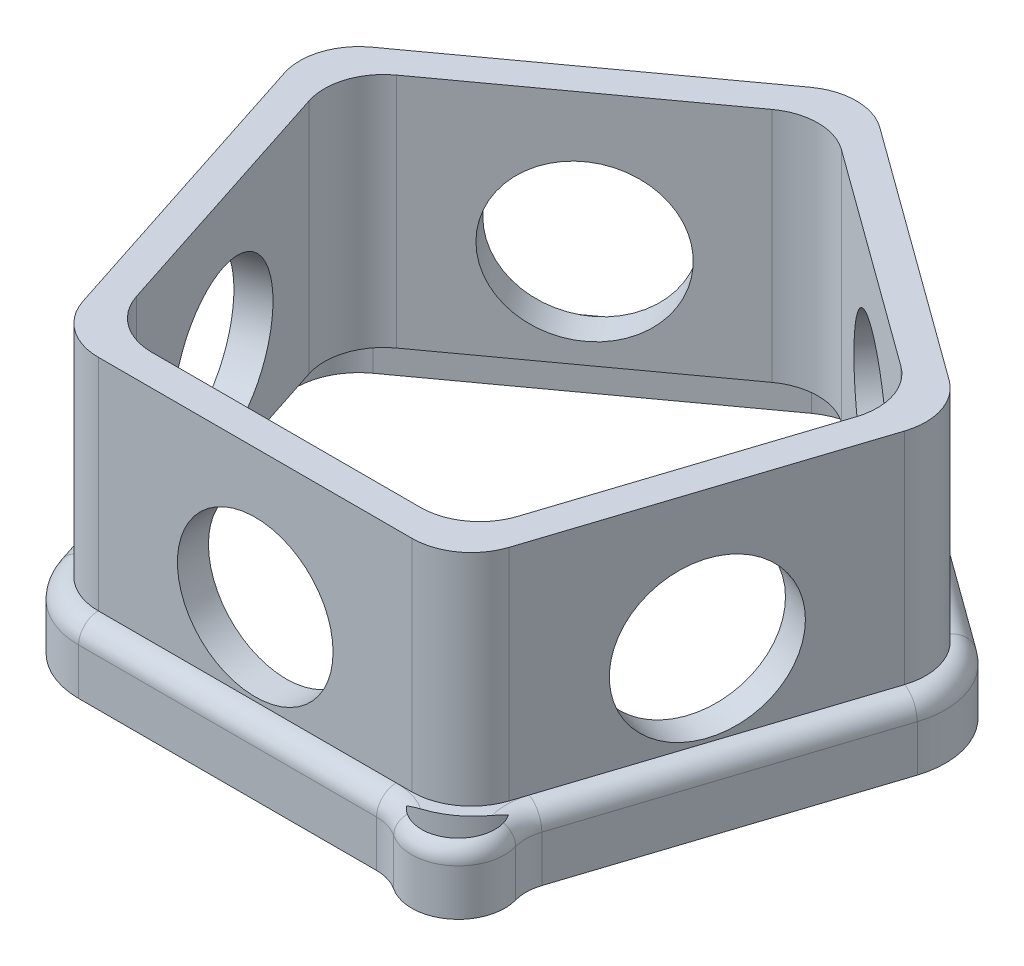
SolidWorks part; units mm, degrees
material "ABS"
ref_plane "Front Plane" through (0, 0, 0) normal (0, 0, 1) x (1, 0, 0)
ref_plane "Top Plane" through (0, 0, 0) normal (0, 1, 0) x (1, 0, 0)
ref_plane "Right Plane" through (0, 0, 0) normal (1, 0, 0) x (0, 0, -1)
sketch "Sketch1" plane through (0, 0, 0) normal (0, 0, 1) x (1, 0, 0)
  line L1 (-22.86, -12.7) -> (22.86, -12.7)
  line L2 (-22.86, -12.7) -> (-22.86, 12.7)
  line L3 (-22.86, 12.7) -> (22.86, 12.7)
  line L4 (22.86, -12.7) -> (22.86, 12.7)
  line L5 (-22.86, -12.7) -> (22.86, 12.7) construction
  line L6 (-22.86, 12.7) -> (22.86, -12.7) construction
  circle A0 centre (0, 0) radius 9.75
  dimension "D1" = 19.5
  dimension "D2" = 45.72
  dimension "D3" = 25.4
extrude "Boss-Extrude1" add sketch "Sketch1" along normal blind 4
sketch "Sketch2" plane through (0, 12.7, 0) normal (0, 1, 0) x (1, 0, 0)
  line L0 (22.86, 0) -> (36.9883, 43.4823)
  line L1 (36.9883, 43.4823) -> (0, 70.3558)
  line L2 (0, 70.3558) -> (-36.9883, 43.4823)
  line L3 (-36.9883, 43.4823) -> (-22.86, 0)
  line L4 (-22.86, 0) -> (22.86, 0)
  line L6 (-41.6905, 45.0102) -> (-25.7662, -4)
  line L7 (-25.7662, -4) -> (25.7662, -4)
  line L8 (25.7662, -4) -> (41.6905, 45.0102)
  line L9 (41.6905, 45.0102) -> (0, 75.3001)
  line L10 (0, 75.3001) -> (-41.6905, 45.0102)
  line L11 (-22.86, 0) -> (-22.86, -4)
  line L12 (-22.86, -4) -> (22.86, 0)
  line L13 (22.86, -4) -> (22.86, 0)
  line M7 (-22.86, 0) -> (-22.86, -4)
  line M9 (22.86, -4) -> (22.86, 0)
  dimension "D1" = 108
  dimension "D2" = 108
  dimension "D3" = 4
extrude "Boss-Extrude2" add sketch "Sketch2" against normal up to surface (25.4 mm away) contours L9 L10 L6 L7 L3 L2 L1 L0 L8 M7 M9 region at (31.0185, 12.7, -21.3856) up to face at (0, -12.7, 2)
sketch "Sketch3" plane through (0, 0, 4) normal (0, 0, 1) x (1, 0, 0)
  circle A0 centre (0, 0) radius 10.033
  dimension "D1" = 20.066
extrude "Cut-Extrude1" cut sketch "Sketch3" against normal blind 11.62
sketch "Sketch4" plane through (0, 12.7, 0) normal (0, 1, 0) x (1, 0, 0)
  line L0 (0, 70.3558) -> (0, 0)
  line L1 (22.86, 0) -> (-22.86, 0) construction
  line L2 (36.9883, 43.4823) -> (-29.9241, 21.7412)
  line L3 (-36.9883, 43.4823) -> (-22.86, 0) construction
sketch "Sketch5" plane through (0, 0, 0) normal (1, 0, 0) x (0, 0, -1)
  line L0 (43.4823, 12.7) -> (21.7412, 12.7) construction
  line L1 (43.4823, 12.7) -> (21.7412, 12.7)
  line L2 (31.5133, 12.7) -> (31.5133, 7.2346)
pattern_circular "CirPattern1" count 5 over 360 about axis through (0, 12.7, -31.5133) along (0, -1, 0) of "Cut-Extrude1"
fillet "Fillet1" radius 7.62 10 edges at (-22.86, 0, 0) (-36.9883, 0, -43.4823) (0, 0, -70.3558) (36.9883, 0, -43.4823) (22.86, 0, 0) (25.7662, 0, 4) (41.6905, 0, -45.0102) (0, 0, -75.3001) (-41.6905, 0, -45.0102) (-25.7662, 0, 4)
sketch "Sketch6" plane through (0, 12.7, 0) normal (0, 1, 0) x (1, 0, 0)
  line L0 (24.5708, 5.2653) -> (35.2775, 38.217) construction
  line L1 (17.3237, 0) -> (-17.3237, 0) construction
  line L2 (-35.2775, 38.217) -> (-24.5708, 5.2653) construction
  line L3 (-4.4789, 67.1017) -> (-32.5093, 46.7364) construction
  line L4 (32.5093, 46.7364) -> (4.4789, 67.1017) construction
  line L5 (-20.2299, -4) -> (20.2299, -4)
  line L6 (27.477, 1.2653) -> (39.9797, 39.7449)
  line L7 (37.2116, 48.2643) -> (4.4789, 72.046)
  line L8 (-4.4789, 72.046) -> (-37.2116, 48.2643)
  line L9 (-39.9797, 39.7449) -> (-27.477, 1.2653)
  line L10 (-20.2299, -4) -> (20.2299, -4)
  line L11 (27.477, 1.2653) -> (39.9797, 39.7449)
  line L12 (37.2116, 48.2643) -> (4.4789, 72.046)
  line L13 (-4.4789, 72.046) -> (-37.2116, 48.2643)
  line L14 (-39.9797, 39.7449) -> (-27.477, 1.2653)
  line L15 (24.5708, 5.2653) -> (35.2775, 38.217)
  line L16 (17.3237, 0) -> (-17.3237, 0)
  line L17 (-35.2775, 38.217) -> (-24.5708, 5.2653)
  line L18 (-4.4789, 67.1017) -> (-32.5093, 46.7364)
  line L19 (32.5093, 46.7364) -> (4.4789, 67.1017)
  arc A0 (35.2775, 38.217) -> (32.5093, 46.7364) centre (28.0304, 40.5717) ccw construction
  arc A1 (17.3237, 0) -> (24.5708, 5.2653) centre (17.3237, 7.62) ccw construction
  arc A2 (-24.5708, 5.2653) -> (-17.3237, 0) centre (-17.3237, 7.62) ccw construction
  arc A3 (-32.5093, 46.7364) -> (-35.2775, 38.217) centre (-28.0304, 40.5717) ccw construction
  arc A4 (4.4789, 67.1017) -> (-4.4789, 67.1017) centre (0, 60.937) ccw construction
  arc A5 (20.2299, -4) -> (27.477, 1.2653) centre (20.2299, 3.62) ccw
  arc A6 (39.9797, 39.7449) -> (37.2116, 48.2643) centre (32.7327, 42.0996) ccw
  arc A7 (4.4789, 72.046) -> (-4.4789, 72.046) centre (0, 65.8813) ccw
  arc A8 (-37.2116, 48.2643) -> (-39.9797, 39.7449) centre (-32.7327, 42.0996) ccw
  arc A9 (-27.477, 1.2653) -> (-20.2299, -4) centre (-20.2299, 3.62) ccw
  arc A10 (20.2299, -4) -> (27.477, 1.2653) centre (20.2299, 3.62) ccw
  arc A11 (39.9797, 39.7449) -> (37.2116, 48.2643) centre (32.7327, 42.0996) ccw
  arc A12 (4.4789, 72.046) -> (-4.4789, 72.046) centre (0, 65.8813) ccw
  arc A13 (-37.2116, 48.2643) -> (-39.9797, 39.7449) centre (-32.7327, 42.0996) ccw
  arc A14 (-27.477, 1.2653) -> (-20.2299, -4) centre (-20.2299, 3.62) ccw
  arc A15 (35.2775, 38.217) -> (32.5093, 46.7364) centre (28.0304, 40.5717) ccw
  arc A16 (17.3237, 0) -> (24.5708, 5.2653) centre (17.3237, 7.62) ccw
  arc A17 (-24.5708, 5.2653) -> (-17.3237, 0) centre (-17.3237, 7.62) ccw
  arc A18 (-32.5093, 46.7364) -> (-35.2775, 38.217) centre (-28.0304, 40.5717) ccw
  arc A19 (4.4789, 67.1017) -> (-4.4789, 67.1017) centre (0, 60.937) ccw
  dimension "D5" = 7.62
  dimension "D6" = 7.62
  dimension "D2" = 4
  dimension "D3" = 40.4598
  dimension "D4" = 34.6475
  dimension "D1" = 0
extrude "Boss-Extrude3" add sketch "Sketch6" along normal blind 5.08
sketch "Sketch7" plane through (-35.8073, 0, -49.2846) normal (-0.5878, 0, -0.809) x (-0.809, 0, 0.5878)
  line L0 (-18.4941, 17.78) -> (-18.4941, 13.97)
  line L1 (-38.724, 17.78) -> (1.7358, 17.78) construction
  circle A0 centre (-18.4941, 13.97) radius 2.5
  dimension "D1" = 5
  dimension "D2" = 3.81
sketch "Sketch8" plane through (0, -12.7, 0) normal (0, -1, 0) x (1, 0, 0)
  line L0 (-27.477, -1.2653) -> (-39.9797, -39.7449) construction
  line L1 (-27.477, -1.2653) -> (-39.9797, -39.7449)
  line L7 (39.9797, -39.7449) -> (27.477, -1.2653)
  line L8 (20.2299, 4) -> (-20.2299, 4)
  line L9 (-27.477, -1.2653) -> (-39.9797, -39.7449)
  line L10 (-37.2116, -48.2643) -> (-4.4789, -72.046)
  line L11 (4.4789, -72.046) -> (37.2116, -48.2643)
  line L12 (39.9797, -39.7449) -> (27.477, -1.2653)
  line L13 (20.2299, 4) -> (-20.2299, 4)
  line L14 (-27.477, -1.2653) -> (-39.9797, -39.7449)
  line L15 (-37.2116, -48.2643) -> (-4.4789, -72.046)
  line L16 (4.4789, -72.046) -> (37.2116, -48.2643)
  line L22 (42.3954, -38.96) -> (29.8927, -0.4804)
  line L23 (20.2299, 6.54) -> (-20.2299, 6.54)
  line L24 (-29.8927, -0.4804) -> (-42.3954, -38.96)
  line L25 (-38.7046, -50.3192) -> (-5.9719, -74.1009)
  line L26 (5.9719, -74.1009) -> (38.7046, -50.3192)
  line L27 (42.3954, -38.96) -> (29.8927, -0.4804)
  line L28 (20.2299, 6.54) -> (-20.2299, 6.54)
  line L29 (-29.8927, -0.4804) -> (-42.3954, -38.96)
  line L30 (-38.7046, -50.3192) -> (-5.9719, -74.1009)
  line L31 (5.9719, -74.1009) -> (38.7046, -50.3192)
  arc A5 (27.477, -1.2653) -> (20.2299, 4) centre (20.2299, -3.62) ccw
  arc A6 (-20.2299, 4) -> (-27.477, -1.2653) centre (-20.2299, -3.62) ccw
  arc A7 (-39.9797, -39.7449) -> (-37.2116, -48.2643) centre (-32.7327, -42.0996) ccw
  arc A8 (-4.4789, -72.046) -> (4.4789, -72.046) centre (0, -65.8813) ccw
  arc A9 (37.2116, -48.2643) -> (39.9797, -39.7449) centre (32.7327, -42.0996) ccw
  arc A10 (27.477, -1.2653) -> (20.2299, 4) centre (20.2299, -3.62) ccw
  arc A11 (-20.2299, 4) -> (-27.477, -1.2653) centre (-20.2299, -3.62) ccw
  arc A12 (-39.9797, -39.7449) -> (-37.2116, -48.2643) centre (-32.7327, -42.0996) ccw
  arc A13 (-4.4789, -72.046) -> (4.4789, -72.046) centre (0, -65.8813) ccw
  arc A14 (37.2116, -48.2643) -> (39.9797, -39.7449) centre (32.7327, -42.0996) ccw
  arc A20 (29.8927, -0.4804) -> (20.2299, 6.54) centre (20.2299, -3.62) ccw
  arc A21 (-20.2299, 6.54) -> (-29.8927, -0.4804) centre (-20.2299, -3.62) ccw
  arc A22 (-42.3954, -38.96) -> (-38.7046, -50.3192) centre (-32.7327, -42.0996) ccw
  arc A23 (-5.9719, -74.1009) -> (5.9719, -74.1009) centre (0, -65.8813) ccw
  arc A24 (38.7046, -50.3192) -> (42.3954, -38.96) centre (32.7327, -42.0996) ccw
  arc A25 (29.8927, -0.4804) -> (20.2299, 6.54) centre (20.2299, -3.62) ccw
  arc A26 (-20.2299, 6.54) -> (-29.8927, -0.4804) centre (-20.2299, -3.62) ccw
  arc A27 (-42.3954, -38.96) -> (-38.7046, -50.3192) centre (-32.7327, -42.0996) ccw
  arc A28 (-5.9719, -74.1009) -> (5.9719, -74.1009) centre (0, -65.8813) ccw
  arc A29 (38.7046, -50.3192) -> (42.3954, -38.96) centre (32.7327, -42.0996) ccw
  line M31 (39.9797, -39.7449) -> (27.477, -1.2653)
  arc M32 (27.477, -1.2653) -> (20.2299, 4) centre (20.2299, -3.62) ccw
  line M33 (20.2299, 4) -> (-20.2299, 4)
  arc M34 (-20.2299, 4) -> (-27.477, -1.2653) centre (-20.2299, -3.62) ccw
  line M35 (-27.477, -1.2653) -> (-39.9797, -39.7449)
  arc M36 (-39.9797, -39.7449) -> (-37.2116, -48.2643) centre (-32.7327, -42.0996) ccw
  line M37 (-37.2116, -48.2643) -> (-4.4789, -72.046)
  arc M38 (-4.4789, -72.046) -> (4.4789, -72.046) centre (0, -65.8813) ccw
  line M39 (4.4789, -72.046) -> (37.2116, -48.2643)
  arc M40 (37.2116, -48.2643) -> (39.9797, -39.7449) centre (32.7327, -42.0996) ccw
  dimension "D1" = 0
  dimension "D2" = 2.54
extrude "Boss-Extrude4" add sketch "Sketch8" along normal blind 6.35 and the other way blind 2.159 contours L31 A29 L27 A25 L28 A26 L29 A27 L30 A28 M31 M40 M39 M38 M37 M36 M35 M34 M33 M32 region at (41.263, -12.7, -44.8712)
sketch "Sketch9" plane through (-37.3003, 0, -51.3395) normal (-0.5878, 0, -0.809) x (-0.809, 0, 0.5878)
  line L0 (1.7358, -12.7) -> (-38.724, -12.7) construction
  line L1 (1.7358, -12.7) -> (-38.724, -12.7)
  line L2 (-18.4941, -12.7) -> (-18.4941, -16.51)
  circle A0 centre (-18.4941, -16.51) radius 1.7
  dimension "D2" = 3.4
  dimension "D1" = 3.81
sketch "Sketch11" plane through (0, -19.05, 0) normal (0, -1, 0) x (1, 0, 0)
  line L0 (20.2299, 6.54) -> (19.9488, 5.4149)
  line L1 (19.9488, 5.4149) -> (27.19, 1.5678)
  line L2 (27.19, 1.5678) -> (29.8927, -0.4804)
  line L5 (5.9719, -74.1009) -> (38.7046, -50.3192)
  line L6 (42.3954, -38.96) -> (29.8927, -0.4804)
  line L7 (20.2299, 6.54) -> (-20.2299, 6.54)
  line L8 (-29.8927, -0.4804) -> (-42.3954, -38.96)
  line L9 (-38.7046, -50.3192) -> (-5.9719, -74.1009)
  line L10 (5.9719, -74.1009) -> (38.7046, -50.3192)
  line L11 (42.3954, -38.96) -> (29.8927, -0.4804)
  line L12 (20.2299, 6.54) -> (-20.2299, 6.54)
  line L13 (-29.8927, -0.4804) -> (-42.3954, -38.96)
  line L14 (-38.7046, -50.3192) -> (-5.9719, -74.1009)
  arc A0 (20.2299, 6.54) -> (29.8927, -0.4804) centre (24.6642, 2.4832) cw
  arc A5 (38.7046, -50.3192) -> (42.3954, -38.96) centre (32.7327, -42.0996) ccw
  arc A6 (29.8927, -0.4804) -> (20.2299, 6.54) centre (20.2299, -3.62) ccw
  arc A7 (-20.2299, 6.54) -> (-29.8927, -0.4804) centre (-20.2299, -3.62) ccw
  arc A8 (-42.3954, -38.96) -> (-38.7046, -50.3192) centre (-32.7327, -42.0996) ccw
  arc A9 (-5.9719, -74.1009) -> (5.9719, -74.1009) centre (0, -65.8813) ccw
  arc A10 (38.7046, -50.3192) -> (42.3954, -38.96) centre (32.7327, -42.0996) ccw
  arc A12 (-20.2299, 6.54) -> (-29.8927, -0.4804) centre (-20.2299, -3.62) ccw
  arc A13 (-42.3954, -38.96) -> (-38.7046, -50.3192) centre (-32.7327, -42.0996) ccw
  arc A14 (-5.9719, -74.1009) -> (5.9719, -74.1009) centre (0, -65.8813) ccw
  arc M24 (29.8927, -0.4804) -> (20.2299, 6.54) centre (20.2299, -3.62) ccw
  dimension "D1" = 0
extrude "Boss-Extrude5" add sketch "Sketch11" against normal up to surface (8.509 mm away) contours L1 L2 L0 M24 | A0 M24 region at (24.8084, -19.05, 3.8811) region at (26.7924, -19.05, 5.4124) up to face at (0, -10.541, -31.4641)
sketch "Sketch12" plane through (0, -19.05, 0) normal (0, -1, 0) x (1, 0, 0)
  line L0 (20.2299, 6.54) -> (20.2299, 4)
  line L1 (29.8927, -0.4804) -> (27.477, -1.2653)
  line L10 (5.9719, -74.1009) -> (38.7046, -50.3192)
  line L11 (42.3954, -38.96) -> (29.8927, -0.4804)
  line L12 (20.2299, 6.54) -> (-20.2299, 6.54)
  line L13 (-29.8927, -0.4804) -> (-42.3954, -38.96)
  line L14 (-38.7046, -50.3192) -> (-5.9719, -74.1009)
  line L15 (42.3954, -38.96) -> (29.8927, -0.4804)
  line L16 (42.3954, -38.96) -> (29.8927, -0.4804)
  line L17 (20.2299, 6.54) -> (-20.2299, 6.54)
  line L18 (20.2299, 6.54) -> (-20.2299, 6.54)
  line L19 (-29.8927, -0.4804) -> (-42.3954, -38.96)
  line L20 (-29.8927, -0.4804) -> (-42.3954, -38.96)
  line L23 (-38.7046, -50.3192) -> (-5.9719, -74.1009)
  line L24 (-38.7046, -50.3192) -> (-5.9719, -74.1009)
  line L25 (5.9719, -74.1009) -> (38.7046, -50.3192)
  line L26 (5.9719, -74.1009) -> (38.7046, -50.3192)
  arc A0 (27.477, -1.2653) -> (20.2299, 4) centre (20.2299, -3.62) ccw construction
  arc A1 (27.477, -1.2653) -> (20.2299, 4) centre (20.2299, -3.62) ccw
  arc A2 (29.8927, -0.4804) -> (20.2299, 6.54) centre (24.6642, 2.4832) ccw
  arc A4 (29.8927, -0.4804) -> (20.2299, 6.54) centre (24.6642, 2.4832) ccw
  arc A6 (28.7878, 0.1459) -> (21.1669, 5.6827) centre (24.6642, 2.4832) ccw
  arc A7 (21.1669, 5.6827) -> (28.7878, 0.1459) centre (19.5024, -4.6213) cw
  arc A14 (38.7046, -50.3192) -> (42.3954, -38.96) centre (32.7327, -42.0996) ccw
  arc A15 (29.8927, -0.4804) -> (20.2299, 6.54) centre (20.2299, -3.62) ccw
  arc A16 (-20.2299, 6.54) -> (-29.8927, -0.4804) centre (-20.2299, -3.62) ccw
  arc A17 (-42.3954, -38.96) -> (-38.7046, -50.3192) centre (-32.7327, -42.0996) ccw
  arc A18 (-5.9719, -74.1009) -> (5.9719, -74.1009) centre (0, -65.8813) ccw
  arc A22 (-20.2299, 6.54) -> (-29.8927, -0.4804) centre (-20.2299, -3.62) ccw
  arc A23 (-20.2299, 6.54) -> (-29.8927, -0.4804) centre (-20.2299, -3.62) ccw
  arc A24 (-42.3954, -38.96) -> (-38.7046, -50.3192) centre (-32.7327, -42.0996) ccw
  arc A25 (-42.3954, -38.96) -> (-38.7046, -50.3192) centre (-32.7327, -42.0996) ccw
  arc A26 (-5.9719, -74.1009) -> (5.9719, -74.1009) centre (0, -65.8813) ccw
  arc A27 (-5.9719, -74.1009) -> (5.9719, -74.1009) centre (0, -65.8813) ccw
  arc A28 (38.7046, -50.3192) -> (42.3954, -38.96) centre (32.7327, -42.0996) ccw
  arc A29 (38.7046, -50.3192) -> (42.3954, -38.96) centre (32.7327, -42.0996) ccw
  dimension "D1" = 0
  dimension "D3" = 1.27
extrude "Cut-Extrude4" cut sketch "Sketch12" against normal blind 12.192 contours A6 | A6 A7 region at (25.7101, -19.05, 3.9228) region at (26.5903, -19.05, 5.1343)
fillet "Fillet5" radius 5.715 2 edges at (29.8927, -14.7955, -0.4804) (20.2299, -14.7955, 6.54)
fillet "Fillet6" radius 2.54 12 edges at (42.3954, -10.541, -45.2392) (22.3382, -10.541, -62.21) (0, -10.541, -76.0413) (-22.3382, -10.541, -62.21) (-42.3954, -10.541, -45.2392) (-36.144, -10.541, -19.7202) (-26.2018, -10.541, 4.5996) (-1.0228, -10.541, 6.54) (19.8337, -10.541, 6.7832) (30.2464, -10.541, -0.782) (36.4601, -10.541, -20.6929) (28.1967, -10.541, 7.3454)
sketch "Sketch13" plane through (0, -19.05, 0) normal (0, -1, 0) x (1, 0, 0)
  line L0 (20.2299, 4.6) -> (-20.2299, 4.6)
  line L1 (-28.0476, -1.0799) -> (-40.5504, -39.5595)
  line L2 (-37.5643, -48.7497) -> (-4.8316, -72.5314)
  line L3 (4.8316, -72.5314) -> (37.5643, -48.7497)
  line L4 (40.5504, -39.5595) -> (28.0476, -1.0799)
  line L5 (39.9797, -39.7449) -> (27.477, -1.2653)
  line L6 (4.4789, -72.046) -> (37.2116, -48.2643)
  line L7 (-37.2116, -48.2643) -> (-4.4789, -72.046)
  line L8 (-27.477, -1.2653) -> (-39.9797, -39.7449)
  line L9 (20.2299, 4) -> (-20.2299, 4)
  line L10 (39.9797, -39.7449) -> (27.477, -1.2653)
  line L11 (4.4789, -72.046) -> (37.2116, -48.2643)
  line L12 (-37.2116, -48.2643) -> (-4.4789, -72.046)
  line L13 (-27.477, -1.2653) -> (-39.9797, -39.7449)
  line L14 (20.2299, 4) -> (-20.2299, 4)
  arc A0 (-20.2299, 4.6) -> (-28.0476, -1.0799) centre (-20.2299, -3.62) ccw
  arc A1 (-40.5504, -39.5595) -> (-37.5643, -48.7497) centre (-32.7327, -42.0996) ccw
  arc A2 (28.7878, 0.1459) -> (21.1669, 5.6827) centre (24.6642, 2.4832) ccw
  arc A3 (28.7878, 0.1459) -> (21.1669, 5.6827) centre (19.5024, -4.6213) ccw
  arc A4 (28.7878, 0.1459) -> (21.1669, 5.6827) centre (24.6642, 2.4832) ccw
  arc A5 (37.2116, -48.2643) -> (39.9797, -39.7449) centre (32.7327, -42.0996) ccw
  arc A6 (-4.4789, -72.046) -> (4.4789, -72.046) centre (0, -65.8813) ccw
  arc A7 (-39.9797, -39.7449) -> (-37.2116, -48.2643) centre (-32.7327, -42.0996) ccw
  arc A8 (-20.2299, 4) -> (-27.477, -1.2653) centre (-20.2299, -3.62) ccw
  arc A9 (27.477, -1.2653) -> (20.2299, 4) centre (20.2299, -3.62) ccw
  arc A10 (37.2116, -48.2643) -> (39.9797, -39.7449) centre (32.7327, -42.0996) ccw
  arc A11 (-4.4789, -72.046) -> (4.4789, -72.046) centre (0, -65.8813) ccw
  arc A12 (-39.9797, -39.7449) -> (-37.2116, -48.2643) centre (-32.7327, -42.0996) ccw
  arc A13 (-20.2299, 4) -> (-27.477, -1.2653) centre (-20.2299, -3.62) ccw
  arc A14 (27.477, -1.2653) -> (20.2299, 4) centre (20.2299, -3.62) ccw
  arc A15 (28.7878, 0.1459) -> (21.1669, 5.6827) centre (19.5024, -4.6213) ccw
  arc A16 (-4.8316, -72.5314) -> (4.8316, -72.5314) centre (0, -65.8813) ccw
  arc A17 (37.5643, -48.7497) -> (40.5504, -39.5595) centre (32.7327, -42.0996) ccw
  arc A18 (28.0476, -1.0799) -> (20.2299, 4.6) centre (20.2299, -3.62) ccw
  dimension "D1" = 0
  dimension "D2" = 0
  dimension "D3" = 0.6
extrude "Cut-Extrude5" cut sketch "Sketch13" against normal up to surface (6.35 mm away) up to face at (0, -12.7, -31.4641)
sketch "Sketch14" plane through (24.4813, 0, 7.9545) normal (0.9511, 0, 0.309) x (0.309, 0, -0.9511)
  line L0 (9.6942, 3.6195) -> (50.154, 3.6195)
  line L1 (43.2591, -7.8105) -> (16.5891, -7.8105)
  line L2 (43.2591, -7.8105) -> (43.2591, 15.0495)
  line L3 (43.2591, 15.0495) -> (16.5891, 15.0495)
  line L4 (16.5891, -7.8105) -> (16.5891, 15.0495)
  line L5 (43.2591, -7.8105) -> (16.5891, 15.0495) construction
  line L6 (43.2591, 15.0495) -> (16.5891, -7.8105) construction
  line L7 (9.6942, 17.78) -> (9.6942, -10.541) construction
  line L8 (50.154, -10.541) -> (50.154, 17.78) construction
  point P0 (29.9241, 3.6195)
  point P11 (29.9241, 3.6195)
  dimension "D1" = 26.67
  dimension "D2" = 22.86
